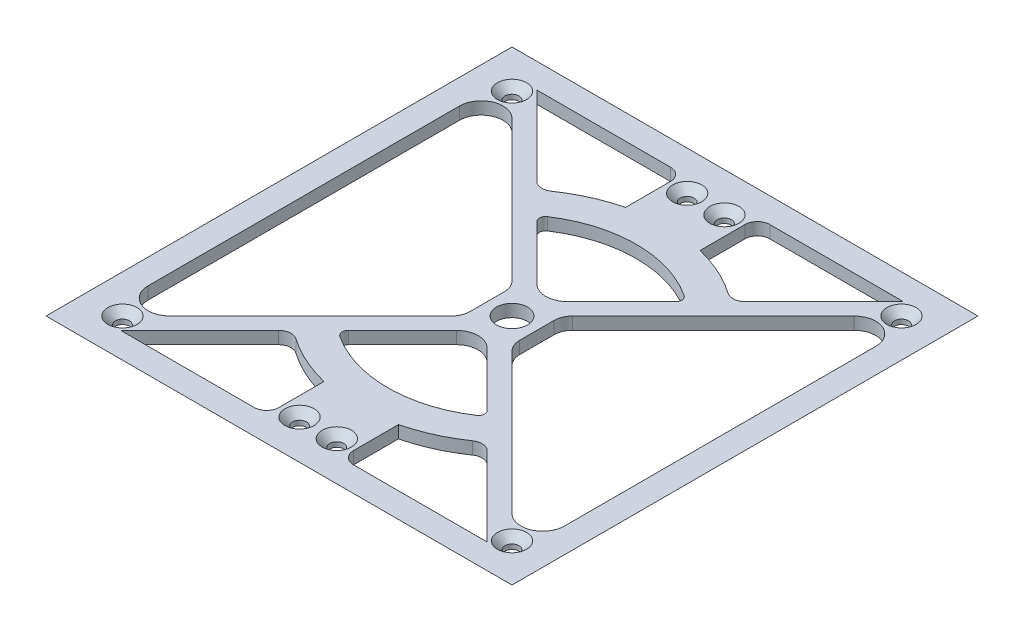
SolidWorks part; units mm, degrees
ref_plane "Front Plane" through (0, 0, 0) normal (0, 0, 1) x (1, 0, 0)
ref_plane "Top Plane" through (0, 0, 0) normal (0, 1, 0) x (1, 0, 0)
ref_plane "Right Plane" through (0, 0, 0) normal (1, 0, 0) x (0, 0, -1)
sketch "Sketch1" plane through (0, 0, 0) normal (0, 1, 0) x (1, 0, 0)
  line L0 (-67, -75) -> (-33.5682, -41.5682)
  line L1 (-75, -75) -> (75, -75)
  line L2 (-75, -75) -> (-75, 75)
  line L3 (-75, 75) -> (75, 75)
  line L4 (75, -75) -> (75, 75)
  line L5 (-75, -75) -> (75, 75) construction
  line L6 (-75, 75) -> (75, -75) construction
  line L7 (-67, -67) -> (-16, -67)
  line L8 (-67, -50.1005) -> (-67, 50.1005)
  line L9 (-67, 67) -> (-16, 67)
  line L10 (67, -50.1005) -> (67, 50.1005)
  line L11 (-67, -67) -> (67, 67) construction
  line L12 (-67, 67) -> (67, -67) construction
  line L13 (0, 75) -> (0, -75)
  line L14 (67, -75) -> (33.5682, -41.5682)
  line L15 (-75, 0) -> (75, 0)
  line L16 (-67, 75) -> (-33.5682, 41.5682)
  line L17 (67, 75) -> (33.5682, 41.5682)
  line L18 (-8, -5.5147) -> (-8, 5.5147)
  line L19 (8, -5.5147) -> (8, 5.5147)
  line L20 (-22.3189, 30.3189) -> (-4.9497, 12.9497)
  line L21 (22.3189, 30.3189) -> (4.9497, 12.9497)
  line L22 (-22.3189, -30.3189) -> (-4.9497, -12.9497)
  line L23 (22.3189, -30.3189) -> (4.9497, -12.9497)
  line L24 (-12, 48.5386) -> (-12, 67) construction
  line L25 (12, -67) -> (12, -48.5386) construction
  line L26 (12, -48.5386) -> (12, -67) construction
  line L27 (-12, -48.5386) -> (-12, -67) construction
  line L28 (16, -67) -> (67, -67)
  line L29 (12, 67) -> (12, 48.5386) construction
  line L30 (16, 67) -> (67, 67)
  line L31 (-55.0503, -55.0503) -> (-9.7574, -9.7574)
  line L32 (9.7574, -9.7574) -> (55.0503, -55.0503)
  line L33 (-55.0503, 55.0503) -> (-9.7574, 9.7574)
  line L34 (9.7574, 9.7574) -> (55.0503, 55.0503)
  line L35 (-12, -48.5386) -> (-12, -63)
  line L36 (12, -48.5386) -> (12, -63)
  line L37 (-12, 48.5386) -> (-12, 63)
  line L38 (12, 48.5386) -> (12, 63)
  arc A0 (-28.4628, -41.108) -> (-12, -48.5386) centre (0, 0) ccw
  arc A1 (28.4628, 41.108) -> (12, 48.5386) centre (0, 0) ccw
  arc A2 (-22.005, -33.4033) -> (22.005, -33.4033) centre (0, 0) ccw
  arc A3 (22.005, 33.4033) -> (-22.005, 33.4033) centre (0, 0) ccw
  arc A4 (12, -48.5386) -> (28.4628, -41.108) centre (0, 0) ccw
  arc A5 (-12, 48.5386) -> (-28.4628, 41.108) centre (0, 0) ccw
  arc A6 (33.5682, 41.5682) -> (28.4628, 41.108) centre (30.7398, 44.3967) cw
  arc A7 (-28.4628, 41.108) -> (-33.5682, 41.5682) centre (-30.7398, 44.3967) cw
  arc A8 (33.5682, -41.5682) -> (28.4628, -41.108) centre (30.7398, -44.3967) ccw
  arc A9 (-28.4628, -41.108) -> (-33.5682, -41.5682) centre (-30.7398, -44.3967) ccw
  arc A10 (22.005, -33.4033) -> (22.3189, -30.3189) centre (20.9047, -31.7331) ccw
  arc A11 (-22.005, -33.4033) -> (-22.3189, -30.3189) centre (-20.9047, -31.7331) cw
  arc A12 (22.005, 33.4033) -> (22.3189, 30.3189) centre (20.9047, 31.7331) cw
  arc A13 (-22.3189, 30.3189) -> (-22.005, 33.4033) centre (-20.9047, 31.7331) cw
  arc A14 (4.9497, -12.9497) -> (-4.9497, -12.9497) centre (0, -17.8995) ccw
  arc A15 (4.9497, 12.9497) -> (-4.9497, 12.9497) centre (0, 17.8995) cw
  arc A16 (67, -50.1005) -> (55.0503, -55.0503) centre (60, -50.1005) cw
  arc A17 (-55.0503, -55.0503) -> (-67, -50.1005) centre (-60, -50.1005) cw
  arc A18 (67, 50.1005) -> (55.0503, 55.0503) centre (60, 50.1005) ccw
  arc A19 (-67, 50.1005) -> (-55.0503, 55.0503) centre (-60, 50.1005) cw
  arc A20 (16, -67) -> (12, -63) centre (16, -63) cw
  arc A21 (-12, -63) -> (-16, -67) centre (-16, -63) cw
  arc A22 (16, 67) -> (12, 63) centre (16, 63) ccw
  arc A23 (-12, 63) -> (-16, 67) centre (-16, 63) ccw
  arc A24 (-8, -5.5147) -> (-9.7574, -9.7574) centre (-14, -5.5147) cw
  arc A25 (8, -5.5147) -> (9.7574, -9.7574) centre (14, -5.5147) ccw
  arc A26 (9.7574, 9.7574) -> (8, 5.5147) centre (14, 5.5147) ccw
  arc A27 (-8, 5.5147) -> (-9.7574, 9.7574) centre (-14, 5.5147) ccw
  point P0 (0, 0)
  point P6 (0, 0)
  point P52 (24, -32)
  point P55 (-24, -32)
  point P58 (24, 32)
  point P61 (-24, 32)
  point P64 (0, -8)
  point P67 (0, 8)
  point P94 (-8, -8)
  point P97 (8, -8)
  point P100 (8, 8)
  point P103 (-8, 8)
  dimension "D5" = 100
  dimension "D7" = 80
  dimension "D9" = 4
  dimension "D10" = 2
  dimension "D11" = 7
  dimension "D12" = 7
  dimension "D13" = 4
  dimension "D14" = 6
  dimension "D1" = 150
  dimension "D2" = 134
  dimension "D3" = 45
  dimension "D4" = 94.7523
  dimension "D6" = 8
  dimension "D8" = 18.4614
extrude "Boss-Extrude2" add sketch "Sketch1" along normal blind 4
sketch "Sketch2" plane through (0, 4, 0) normal (0, 1, 0) x (1, 0, 0)
  line L0 (-67, 50.1005) -> (-67, 75)
  line L1 (-75, 75) -> (75, 75) construction
  line L2 (-59, 67) -> (-75, 67)
  line L3 (-75, -75) -> (-75, 75) construction
  line L4 (0, -75) -> (0, 75)
  line L5 (-75, -75) -> (75, -75) construction
  line L6 (-75, 0) -> (75, 0)
  line L7 (75, -75) -> (75, 75) construction
  line L8 (-12, 67) -> (0, 67) construction
  line L9 (-12, 48.5386) -> (12, 48.5386)
  line L10 (-12, 48.5386) -> (-12, 67)
  line L11 (12, 48.5386) -> (12, 67)
  line L12 (-12, 67) -> (12, 48.5386)
  line L13 (-12, 48.5386) -> (12, 67)
  line L14 (-12, 67) -> (0, 67) construction
  line L15 (0, 67) -> (12, 67) construction
  line L16 (0, 67) -> (12, 67) construction
  line L17 (-6, 67) -> (-6, 48.5386)
  line L18 (6, 67) -> (6, 48.5386)
  line L19 (-16, 67) -> (-12, 67)
  line L20 (12, 67) -> (16, 67)
  circle A0 centre (-62.6878, 62.6878) radius 4.3122
  circle A1 centre (-62.6878, 62.6878) radius 3
  circle A2 centre (62.6878, 62.6878) radius 3
  circle A5 centre (62.6878, -62.6878) radius 3
  circle A7 centre (-62.6878, -62.6878) radius 3
  circle A8 centre (-6, 62.3847) radius 2
  circle A9 centre (6, 62.3847) radius 2
  circle A10 centre (-6, 53.154) radius 2
  circle A11 centre (6, 53.154) radius 2
  circle A12 centre (6, -53.154) radius 2
  circle A13 centre (-6, -53.154) radius 2
  circle A14 centre (-6, -62.3847) radius 2
  circle A15 centre (6, -62.3847) radius 2
  circle A16 centre (0, 0) radius 5
  dimension "D1" = 8.6243
  dimension "D2" = 6
  dimension "D4" = 4
  dimension "D3" = 6
extrude "Cut-Extrude1" cut sketch "Sketch2" against normal through all contours L4 A16 L6 | L6 A16 L4 | L4 A16 L6 | L6 A16 L4 | A11 | A10
sketch "Sketch3" plane through (0, 4, 0) normal (0, 1, 0) x (1, 0, 0)
  line L0 (-67, 50.1005) -> (-67, 75)
  line L1 (-75, 75) -> (75, 75) construction
  line L2 (-59, 67) -> (-75, 67)
  line L3 (-75, -75) -> (-75, 75) construction
  circle A0 centre (-62.6878, 62.6878) radius 4.3122
  circle A1 centre (-62.6878, 62.6878) radius 2
  point P11 (-62.6878, 62.6878)
  dimension "D1" = 8.6243
  dimension "D2" = 4
hole_wizard "CSK for M4 Flat Head Machine Screw1" positions "Sketch3" profile "Sketch4" countersink size "M4" standard "ANSI Metric" end condition through all
sketch "Sketch4" plane through (-62.6878, 4, -62.6878) normal (1, 0, 0) x (0, 0, 1)
  line L0 (0, 0) -> (0, 4)
  line L1 (0, 4) -> (2.25, 4)
  line L2 (2.25, 4) -> (2.25, 2.45)
  line L3 (2.25, 2.45) -> (4.7, 0)
  line L5 (4.7, 0) -> (0, 0)
  line L6 (-2.25, 2.45) -> (-4.7, 0) construction
  line L11 (0, -6.35) -> (0, 107.95) construction
  dimension "Thru Hole Dia." = 4.5
  dimension "Thru Hole Depth" = 4
  dimension "Near C'Sink Dia." = 9.4
  dimension "Near C'Sink Angle" = 90
mirror "Mirror1" about plane through (0, 0, 0) normal (0, 0, 1) of "CSK for M4 Flat Head Machine Screw1" second plane through (0, 0, 0) second plane normal (1, 0, 0)
sketch "Sketch5" plane through (0, 4, 0) normal (0, 1, 0) x (1, 0, 0)
  line L0 (-12, 48.5386) -> (12, 48.5386)
  line L2 (-75, 75) -> (75, 75) construction
  line L3 (-12, 63) -> (-12, 75)
  line L4 (12, 63) -> (12, 75)
  line L5 (-12, 67) -> (0, 67)
  line L6 (0, 67) -> (12, 67)
  line L9 (-6, 67) -> (-6, 48.5386)
  line L10 (6, 67) -> (6, 48.5386)
  line L14 (0, 67) -> (0, 75)
  circle A0 centre (-6, 62.3847) radius 2
  circle A1 centre (6, 62.3847) radius 2
  circle A2 centre (6, 53.154) radius 2
  circle A3 centre (-6, 53.154) radius 2
  point P22 (-6, 62.3847)
  point P24 (6, 62.3847)
  point P31 (6, 53.154)
  point P33 (-6, 53.154)
hole_wizard "CSK for M4 Flat Head Machine Screw2" positions "Sketch5" profile "Sketch10" countersink size "M4" standard "ANSI Metric"
sketch "Sketch10" plane through (6, 4, -62.3847) normal (1, 0, 0) x (0, 0, 1)
  line L0 (0, 0) -> (0, 4)
  line L1 (0, 4) -> (2.25, 4)
  line L2 (2.25, 4) -> (2.25, 2.45)
  line L3 (2.25, 2.45) -> (4.7, 0)
  line L5 (4.7, 0) -> (0, 0)
  line L6 (-2.25, 2.45) -> (-4.7, 0) construction
  line L11 (0, -6.35) -> (0, 107.95) construction
  dimension "Thru Hole Dia." = 4.5
  dimension "Thru Hole Depth" = 4
  dimension "Near C'Sink Dia." = 9.4
  dimension "Near C'Sink Angle" = 90
mirror "Mirror2" about plane through (0, 0, 0) normal (0, 0, 1) of "CSK for M4 Flat Head Machine Screw2"
chamfer "Chamfer1" distance 4 angle 45 4 edges at (0, 0, -75) (-75, 0, 0) (0, 0, 75) (75, 0, 0)
